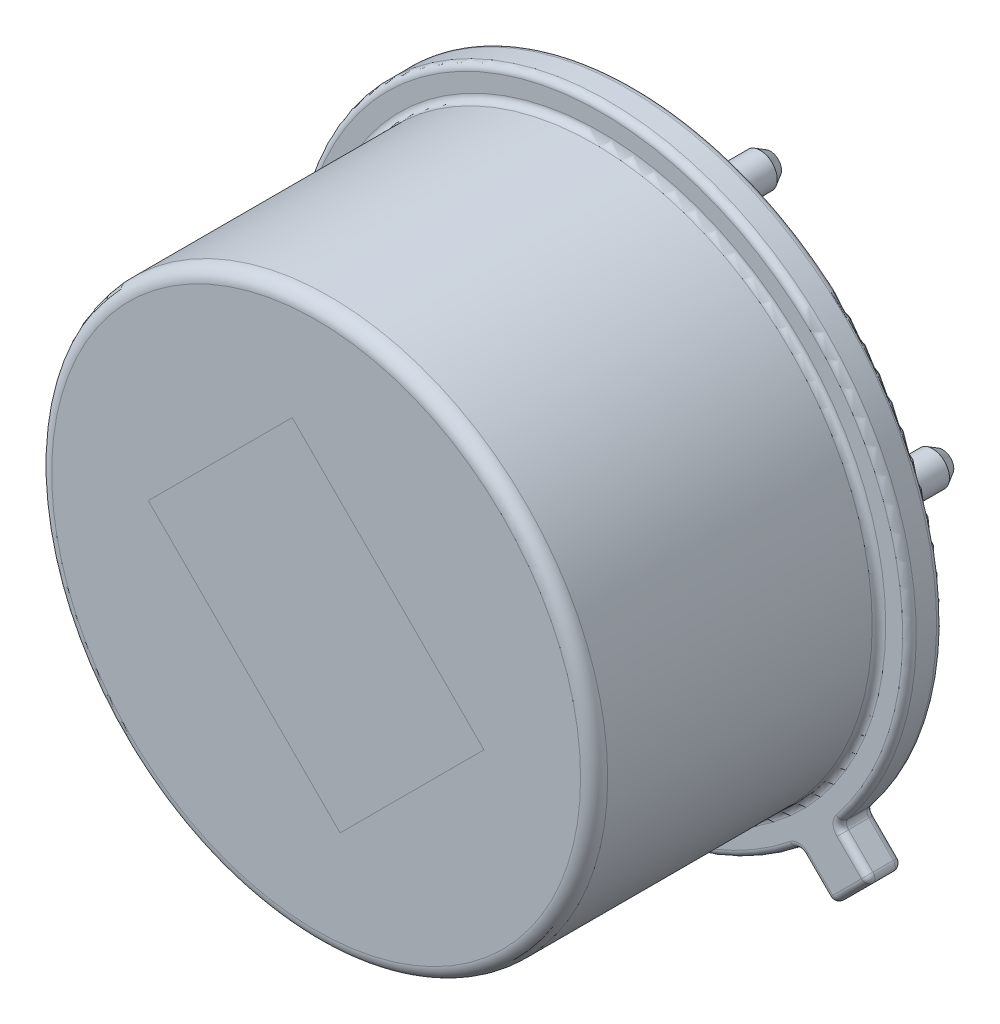
SolidWorks part; units mm, degrees
ref_plane "Front Plane" through (0, 0, 0) normal (0, 0, 1) x (1, 0, 0)
ref_plane "Top Plane" through (0, 0, 0) normal (0, 1, 0) x (1, 0, 0)
ref_plane "Right Plane" through (0, 0, 0) normal (1, 0, 0) x (0, 0, -1)
sketch "Sketch1" plane through (0, 0, 0) normal (0, 0, 1) x (1, 0, 0)
  line L0 (0, 0) -> (6.5502, 0) construction
  line L1 (0, 0) -> (3.6999, -3.6999) construction
  line L2 (3.9827, -3.417) -> (3.417, -3.9827)
  line L3 (3.9827, -3.417) -> (3.4877, -2.922)
  line L4 (3.417, -3.9827) -> (2.922, -3.4877)
  arc A0 (3.4877, -2.922) -> (2.922, -3.4877) centre (0, 0) ccw
  dimension "D1" = 45
  dimension "D2" = 9.1
  dimension "D3" = 0.8
  dimension "D4" = 0.7
extrude "Extrude1" add sketch "Sketch1" along normal blind 0.5
sketch "Sketch2" plane through (0, 0, 0.5) normal (0, 0, 1) x (1, 0, 0)
  circle A0 centre (0, 0) radius 4.1
  dimension "D1" = 8.2
extrude "Extrude2" add sketch "Sketch2" along normal blind 4.2
sketch "Sketch3" plane through (0, 0, 4.7) normal (0, 0, 1) x (1, 0, 0)
  line L0 (0, 0) -> (4.1, 0) construction
  line L1 (0, 0) -> (2.8991, -2.8991) construction
  line L2 (-2.4749, 0.3536) -> (0.3536, -2.4749)
  line L3 (-2.4749, 0.3536) -> (-0.3536, 2.4749)
  line L4 (0.3536, -2.4749) -> (2.4749, -0.3536)
  line L5 (-0.3536, 2.4749) -> (2.4749, -0.3536)
  line L6 (-2.4749, 0.3536) -> (2.4749, -0.3536) construction
  line L7 (0.3536, -2.4749) -> (-0.3536, 2.4749) construction
  circle A0 centre (0, 0) radius 4.1 construction
  dimension "D1" = 45
  dimension "D2" = 4
  dimension "D3" = 3
extrude "Extrude3" cut sketch "Sketch3" against normal blind 0.9
sketch "Sketch4" plane through (0, 0, 0) normal (0, 0, -1) x (-1, 0, 0)
  line L0 (-4.55, 0) -> (4.55, 0) construction
  line L1 (0, 4.55) -> (0, -4.55) construction
  arc A0 (-2.922, -3.4877) -> (-3.4877, -2.922) centre (0, 0) ccw construction
  circle A1 centre (-2.54, 0) radius 0.25
  circle A2 centre (0, 2.54) radius 0.25
  circle A3 centre (2.54, 0) radius 0.25
  dimension "D1" = 0.5
  dimension "D2" = 2.54
  dimension "D3" = 2.54
  dimension "D4" = 2.54
extrude "Extrude4" add sketch "Sketch4" along normal blind 2
sketch "Sketch5" plane through (0, 0, 3.8) normal (0, 0, 1) x (1, 0, 0)
  line L0 (-0.3536, 2.4749) -> (2.4749, -0.3536)
  line L1 (2.4749, -0.3536) -> (0.3536, -2.4749)
  line L2 (0.3536, -2.4749) -> (-2.4749, 0.3536)
  line L3 (-2.4749, 0.3536) -> (-0.3536, 2.4749)
extrude "Extrude5" add sketch "Sketch5" along normal blind 0.9 separate body
fillet "Fillet1" radius 0.2 1 edges at (4.1, 0, 4.7)
fillet "Fillet2" radius 0.1 16 edges at (-2.29, 0, 0) (2.79, 0, 0) (-3.2173, 3.2173, 0) (3.1695, -3.7352, 0) (3.6999, -3.6999, 0) (3.7352, -3.1695, 0) (0.25, 2.54, 0) (4.1, 0, 0.5) (3.6999, -3.6999, 0.5) (3.1695, -3.7352, 0.5) (-3.2173, 3.2173, 0.5) (3.7352, -3.1695, 0.5) (2.922, -3.4877, 0.25) (3.417, -3.9827, 0.25) (3.9827, -3.417, 0.25) (3.4877, -2.922, 0.25)
chamfer "Chamfer1" distance 0.15 angle 30 3 edges at (-2.79, 0, -2) (-0.25, 2.54, -2) (2.29, 0, -2) first distance on face at (-2.29, 0, -0.1) first distance on face at (0.25, 2.54, -0.1) first distance on face at (2.79, 0, -0.1)
